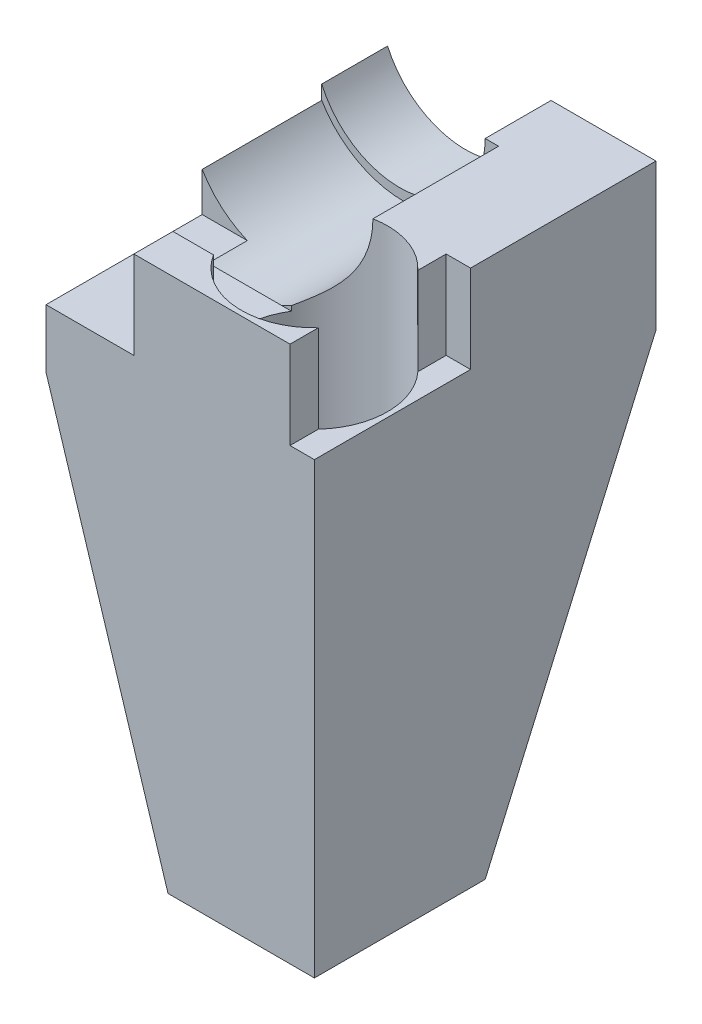
SolidWorks part; units mm, degrees
ref_plane "Front Plane" through (0, 0, 0) normal (0, 0, 1) x (1, 0, 0)
ref_plane "Top Plane" through (0, 0, 0) normal (0, 1, 0) x (1, 0, 0)
ref_plane "Right Plane" through (0, 0, 0) normal (1, 0, 0) x (0, 0, -1)
sketch "Sketch1" plane through (0, 0, 0) normal (0, 1, 0) x (1, 0, 0)
  line L1 (0, 0) -> (55, 0)
  line L2 (0, 0) -> (0, 70)
  line L3 (0, 70) -> (55, 70)
  line L4 (55, 0) -> (55, 70)
  dimension "D1" = 55
  dimension "D2" = 70
extrude "Boss-Extrude1" add sketch "Sketch1" along normal blind 110
sketch "Sketch2" plane through (0, 110, 0) normal (0, 1, 0) x (1, 0, 0)
  line L0 (55, 0) -> (55, 70) construction
  line L1 (0, 0) -> (55, 0) construction
  circle A0 centre (39, 16) radius 15
  dimension "D1" = 30
  dimension "D2" = 16
  dimension "D3" = 16
extrude "Cut-Extrude1" cut sketch "Sketch2" against normal blind 108
sketch "Sketch3" plane through (0, 110, 0) normal (0, 1, 0) x (1, 0, 0)
  line L0 (0, 0) -> (55, 0) construction
  line L1 (55, 0) -> (50, 0)
  line L2 (55, 0) -> (55, 32)
  line L3 (55, 32) -> (50, 32)
  line L4 (50, 0) -> (50, 32)
  line L5 (0, 0) -> (18, 0)
  line L6 (0, 0) -> (0, 32)
  line L7 (0, 32) -> (18, 32)
  line L8 (18, 0) -> (18, 8)
  line L9 (18, 8) -> (31.3328, 8)
  line L11 (18, 24) -> (31.3328, 24)
  line L12 (31.3328, 8) -> (31.3328, 24)
  line L13 (18, 24) -> (18, 32)
  dimension "D1" = 32
  dimension "D2" = 5
  dimension "D3" = 32
  dimension "D4" = 18
  dimension "D5" = 16
  dimension "D6" = 8
extrude "Cut-Extrude2" cut sketch "Sketch3" against normal blind 18
sketch "Sketch4" plane through (0, 0, -70) normal (0, 0, -1) x (-1, 0, 0)
  line L0 (-55, 110) -> (0, 110) construction
  line L2 (0, 110) -> (0, 0) construction
  circle A0 centre (-16, 110) radius 17.5
  dimension "D1" = 35
  dimension "D3" = 16
  dimension "D2" = 0
extrude "Cut-Extrude3" cut sketch "Sketch4" against normal blind 13.5 contours A0
sketch "Sketch5" plane through (0, 0, -56.5) normal (0, 0, -1) x (-1, 0, 0)
  line L0 (0, 110) -> (-33.5, 110) construction
  circle A0 centre (-16.75, 110) radius 19.5
  dimension "D1" = 39
extrude "Cut-Extrude5" cut sketch "Sketch5" against normal up to surface (32.5 mm away) up to face at (22.1557, 101, -24)
sketch "Sketch8" plane through (55, 0, 0) normal (1, 0, 0) x (0, 0, -1)
  line L0 (70, 0) -> (70, 80)
  line L1 (70, 110) -> (70, 0) construction
  line L2 (70, 80) -> (35, 0)
  line L3 (0, 0) -> (70, 0) construction
  line L4 (35, 0) -> (70, 0)
  dimension "D1" = 35
  dimension "D2" = 80
extrude "Cut-Extrude7" cut sketch "Sketch8" against normal up to next
sketch "Sketch9" plane through (0, 0, 0) normal (0, 0, 1) x (1, 0, 0)
  line L0 (0, 0) -> (25, 0)
  line L1 (0, 0) -> (55, 0) construction
  line L2 (25, 0) -> (0, 80)
  line L3 (0, 92) -> (0, 0) construction
  line L4 (0, 80) -> (0, 0)
  dimension "D1" = 80
  dimension "D2" = 25
extrude "Cut-Extrude8" cut sketch "Sketch9" against normal up to next
